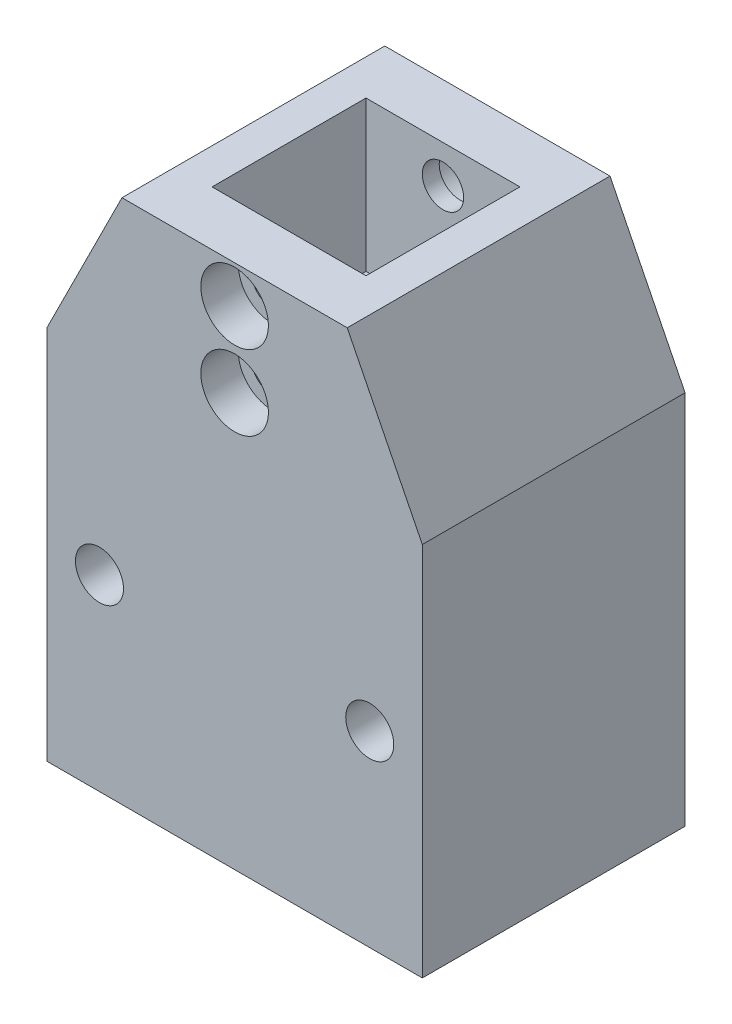
SolidWorks part; units mm, degrees
ref_plane "Front Plane" through (0, 0, 0) normal (0, 0, 1) x (1, 0, 0)
ref_plane "Top Plane" through (0, 0, 0) normal (0, 1, 0) x (1, 0, 0)
ref_plane "Right Plane" through (0, 0, 0) normal (1, 0, 0) x (0, 0, -1)
sketch "Sketch1" plane through (0, 0, 0) normal (0, 0, 1) x (1, 0, 0)
  line L0 (-25, 25) -> (-15, 45)
  line L1 (25, -25) -> (-25, -25)
  line L2 (25, -25) -> (25, 25)
  line L4 (-25, -25) -> (-25, 25)
  line L5 (25, -25) -> (-25, 25) construction
  line L6 (25, 25) -> (-25, -25) construction
  line L7 (-15, 45) -> (15, 45)
  line L8 (15, 45) -> (25, 25)
  point P0 (0, 0)
  point P6 (0, 45)
  dimension "D1" = 30
  dimension "D2" = 50
  dimension "D4" = 70
extrude "Body" add sketch "Sketch1" along normal mid plane 35
sketch "Sketch4" plane through (0, 45, 0) normal (0, 1, 0) x (1, 0, 0)
  line L1 (10.25, -10.25) -> (-10.25, -10.25)
  line L2 (10.25, -10.25) -> (10.25, 10.25)
  line L3 (10.25, 10.25) -> (-10.25, 10.25)
  line L4 (-10.25, -10.25) -> (-10.25, 10.25)
  line L5 (10.25, -10.25) -> (-10.25, 10.25) construction
  line L6 (10.25, 10.25) -> (-10.25, -10.25) construction
  point P0 (0, 0)
  dimension "D1" = 20.5
extrude "Profil_Hole" cut sketch "Sketch4" against normal blind 20
hole_wizard "M5 Clearance Hole1" positions "Sketch8" profile "Sketch9" hole size "M5" standard "ANSI Metric" end condition through all
sketch "Sketch8" plane through (0, 0, -17.5) normal (0, 0, -1) x (-1, 0, 0)
  line L0 (0, 40) -> (0, 30) construction
  line L2 (-15, 45) -> (15, 45) construction
  point P0 (0, 40)
  point P3 (0, 30)
  dimension "D1" = 5
  dimension "D2" = 10
sketch "Sketch9" plane through (0, 40, -17.5) normal (1, 0, 0) x (0, 1, 0)
  line L0 (0, 0) -> (0, 35)
  line L1 (0, 35) -> (2.75, 35)
  line L2 (2.75, 35) -> (2.75, 0)
  line L5 (2.75, 0) -> (0, 0)
  line L11 (0, -6.35) -> (0, 107.95) construction
  dimension "Thru Hole Dia." = 5.5
  dimension "Thru Hole Depth" = 35
sketch "Sketch14" plane through (0, 0, -17.5) normal (0, 0, -1) x (-1, 0, 0)
  circle A0 centre (0, 0) radius 7.5
  dimension "D1" = 15
extrude "Bearing_Support" add sketch "Sketch14" along normal blind 4
sketch "Sketch15" plane through (0, 0, -21.5) normal (0, 0, -1) x (-1, 0, 0)
  circle A0 centre (0, 0) radius 4.7
  circle A1 centre (0, 0) radius 7.5
  circle A2 centre (0, 0) radius 7.5
  dimension "D2" = 9.4
  dimension "D1" = 0
extrude "Bearing_Place" add sketch "Sketch15" along normal blind 4
sketch "Sketch16" plane through (0, 0, -21.5) normal (0, 0, -1) x (-1, 0, 0)
  circle A0 centre (0, 0) radius 2
  dimension "D1" = 4
extrude "Shaft_Place" cut sketch "Sketch16" against normal blind 3
sketch "Sketch17" plane through (0, 0, 17.5) normal (0, 0, 1) x (1, 0, 0)
  line L0 (0, -1000.3535) -> (0, 48999.6465) construction
  circle A0 centre (-18, 0) radius 3.2
  circle A1 centre (18, 0) radius 3.2
  dimension "D1" = 6.4
  dimension "D2" = 18
extrude "Inserts_Holes" cut sketch "Sketch17" against normal blind 9.5
fillet "Fillet1" radius 6 1 edges at (-7.5, 0, -17.5)
sketch "Sketch19" plane through (0, 0, -17.5) normal (0, 0, -1) x (-1, 0, 0)
  circle A0 centre (0, 40) radius 4.5
  circle A1 centre (0, 30) radius 4.5
  dimension "D1" = 9
extrude "M5_Screw_Place" cut sketch "Sketch19" against normal blind 5
mirror "Mirror1" about plane through (0, 0, 0) normal (0, 0, 1) of "M5_Screw_Place"
